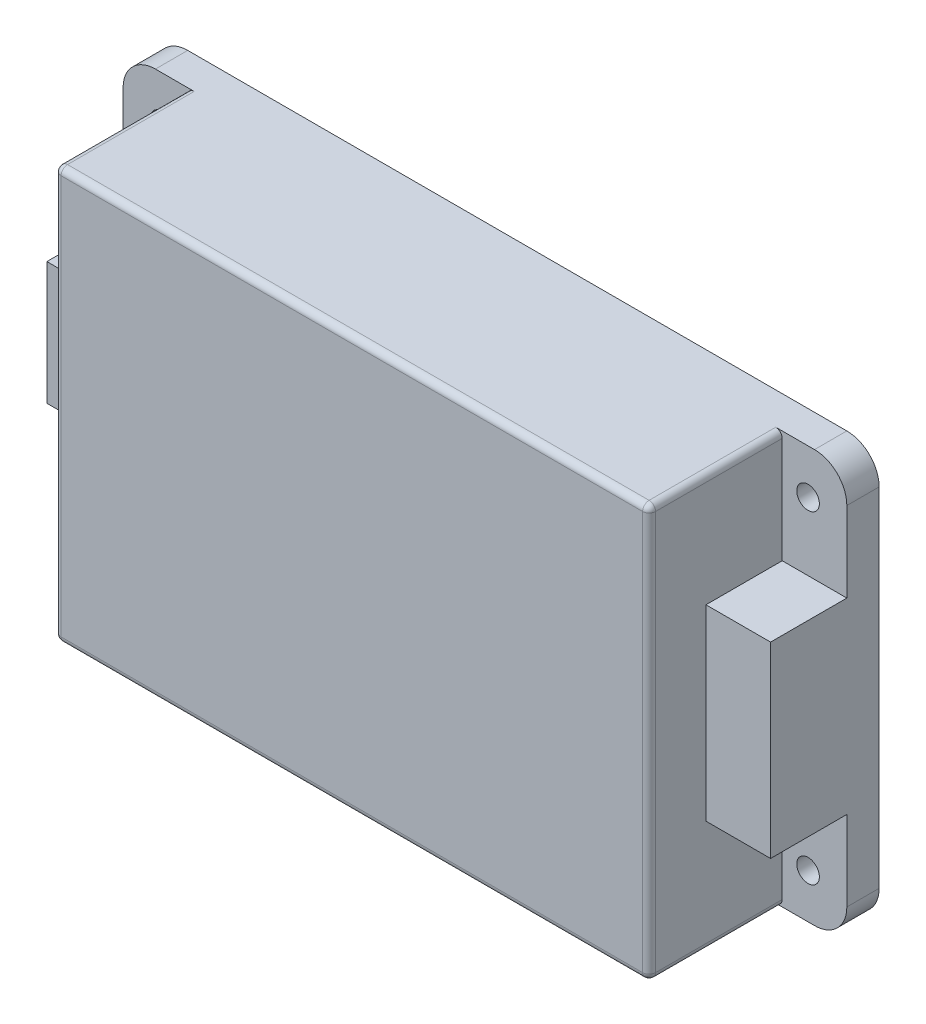
SolidWorks part; units mm, degrees
ref_plane "Front Plane" through (0, 0, 0) normal (0, 0, 1) x (1, 0, 0)
ref_plane "Top Plane" through (0, 0, 0) normal (0, 1, 0) x (1, 0, 0)
ref_plane "Right Plane" through (0, 0, 0) normal (1, 0, 0) x (0, 0, -1)
sketch "Sketch1" plane through (0, 0, 0) normal (0, 0, 1) x (1, 0, 0)
  line L0 (-135.4838, 31.9) -> (135.4838, 31.9) construction
  line L1 (0, 0) -> (-112, 0)
  line L2 (0, 0) -> (0, 63.8)
  line L3 (0, 63.8) -> (-112, 63.8)
  line L4 (-112, 0) -> (-112, 63.8)
  line L5 (-56, 70.0509) -> (-56, -13.9249) construction
  circle A0 centre (-106, 56.9) radius 1.75
  circle A1 centre (-6, 56.9) radius 1.75
  circle A2 centre (-6, 6.9) radius 1.75
  circle A3 centre (-106, 6.9) radius 1.75
  point P7 (0, 31.9)
  point P12 (-56, 63.8)
  dimension "D3" = 25
  dimension "D1" = 63.8
  dimension "D2" = 112
  dimension "D4" = 50
extrude "Boss-Extrude1" add sketch "Sketch1" along normal blind 5
sketch "Sketch2" plane through (0, 0, 5) normal (0, 0, 1) x (1, 0, 0)
  line L0 (0, 63.8) -> (-112, 63.8) construction
  line L1 (-102, 63.8) -> (-10, 63.8)
  line L2 (-102, 63.8) -> (-102, 0)
  line L3 (-102, 0) -> (-10, 0)
  line L4 (-10, 63.8) -> (-10, 0)
  line L5 (-112, 0) -> (0, 0) construction
  line L6 (-112, 63.8) -> (-112, 0) construction
  dimension "D1" = 10
  dimension "D2" = 92
extrude "Boss-Extrude2" add sketch "Sketch2" along normal blind 20.6
sketch "Sketch3" plane through (0, 0, 5) normal (0, 0, 1) x (1, 0, 0)
  line L0 (-117.9486, 31.9) -> (17.6718, 31.9) construction
  line L1 (-112, 63.8) -> (-112, 0) construction
  line L2 (-102, 63.8) -> (-102, 0) construction
  line L3 (-112, 41.4) -> (-102, 41.4)
  line L4 (-112, 41.4) -> (-112, 22.4)
  line L5 (-112, 22.4) -> (-102, 22.4)
  line L6 (-102, 41.4) -> (-102, 22.4)
  line L7 (-10, 0) -> (-10, 63.8) construction
  line L8 (-10, 46.4) -> (0, 46.4)
  line L9 (-10, 46.4) -> (-10, 17.4)
  line L10 (-10, 17.4) -> (0, 17.4)
  line L11 (0, 46.4) -> (0, 17.4)
  line L12 (0, 0) -> (0, 63.8) construction
  point P4 (-112, 31.9)
  point P11 (-112, 31.9)
  point P20 (0, 31.9)
  dimension "D1" = 19
  dimension "D2" = 29
extrude "Boss-Extrude3" add sketch "Sketch3" along normal blind 11.8
fillet "Fillet1" radius 5 4 edges at (-112, 0, 2.5) (0, 0, 2.5) (0, 63.8, 2.5) (-112, 63.8, 2.5)
fillet "Fillet2" radius 1 4 edges at (-56, 63.8, 25.6) (-10, 31.9, 25.6) (-56, 0, 25.6) (-102, 31.9, 25.6)
fillet "Fillet3" radius 1 8 edges at (-10.2929, 0.2929, 25.3071) (-10.2929, 63.5071, 25.3071) (-101.7071, 63.5071, 25.3071) (-101.7071, 0.2929, 25.3071) (-10, 0, 14.8) (-10, 63.8, 14.8) (-102, 63.8, 14.8) (-102, 0, 14.8)
